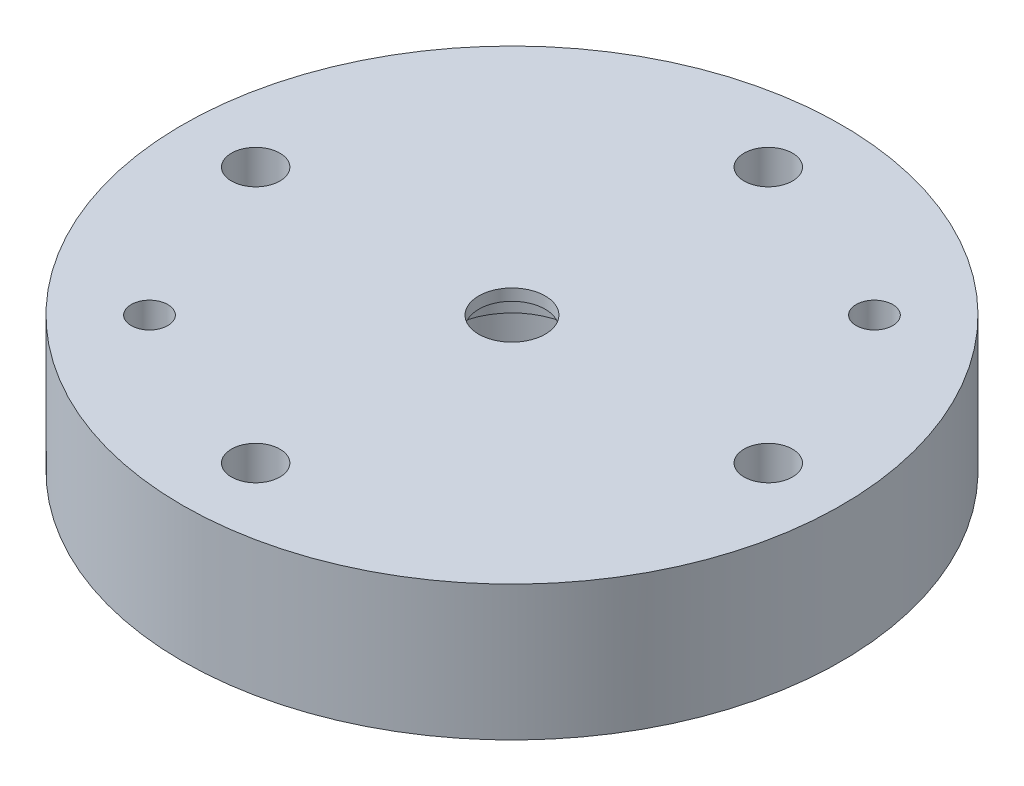
SolidWorks part; units mm, degrees
ref_plane "Front Plane" through (0, 0, 0) normal (0, 0, 1) x (1, 0, 0)
ref_plane "Top Plane" through (0, 0, 0) normal (0, 1, 0) x (1, 0, 0)
ref_plane "Right Plane" through (0, 0, 0) normal (1, 0, 0) x (0, 0, -1)
sketch "Sketch1" plane through (0, 0, 0) normal (0, 1, 0) x (1, 0, 0)
  circle A0 centre (0, 0) radius 57.15
  dimension "D1" = 114.3
extrude "seal seat hieght" add sketch "Sketch1" against normal blind 5.5372 contours A0
ref_plane "top end of seal" through (0, 0, 0) normal (0, 1, 0) x (1, 0, 0)
sketch "Sketch2" plane through (0, -5.5372, 0) normal (0, -1, 0) x (1, 0, 0)
  circle A1 centre (0, 0) radius 57.15
  circle A2 centre (0, 0) radius 57.15
  dimension "D1" = 0
extrude "seal diaphram hieght" add sketch "Sketch2" along normal blind 15.875
ref_plane "bottom end of seal" through (0, -21.4122, 0) normal (0, -1, 0) x (-1, 0, 0)
sketch "Sketch3" plane through (0, 0, 0) normal (0, 1, 0) x (1, 0, 0)
  circle A1 centre (0, 0) radius 57.15
  circle A2 centre (0, 0) radius 57.15
  dimension "D1" = 0
extrude "seal shoulder hieght" add sketch "Sketch3" along normal blind 2
sketch "Sketch4" plane through (0, -21.4122, 0) normal (0, -1, 0) x (1, 0, 0)
  circle A1 centre (0, 0) radius 57.15
  circle A2 centre (0, 0) radius 57.15
  dimension "D1" = 0
sketch "Sketch5" plane through (0, 0, 0) normal (0, 1, 0) x (1, 0, 0)
  circle A0 centre (0, 0) radius 11.1125
  dimension "D1" = 22.225
extrude "seal seat fit" cut sketch "Sketch5" against normal blind 5.5372
sketch "Sketch6" plane through (0, -21.4122, 0) normal (0, -1, 0) x (-1, 0, 0)
  circle A0 centre (0, 0) radius 12.7
  dimension "D1" = 25.4
sketch "Sketch7" plane through (0, 0, 0) normal (0, 1, 0) x (1, 0, 0)
  circle A0 centre (0, 0) radius 4.7625 construction
  circle A1 centre (0, 0) radius 5.7625
  dimension "D1" = 9.525
  dimension "D2" = 1
extrude "shaft clearance" cut sketch "Sketch7" along normal up to surface (2 mm away) up to face at (0, 2, 57.15)
sketch "bolt circle" plane through (0, 2, 0) normal (0, 1, 0) x (1, 0, 0)
  circle A0 centre (0, 0) radius 44.45 construction
  point P3 (-44.45, 0)
  point P4 (0, 44.45)
  point P5 (44.45, 0)
  point P6 (0, -44.45)
  dimension "D1" = 88.9
hole_wizard "M8 Clearance Hole1" positions "Sketch11" profile "Sketch12" hole size "M8" standard "ANSI Metric" end condition through all
sketch "Sketch11" plane through (0, 2, 0) normal (0, 1, 0) x (1, 0, 0)
  point P0 (-44.45, 0)
  point P3 (0, 44.45)
  point P6 (44.45, 0)
  point P9 (0, -44.45)
sketch "Sketch12" plane through (-44.45, 2, 0) normal (1, 0, 0) x (0, 0, 1)
  line L0 (0, 0) -> (0, 23.4122)
  line L1 (0, 23.4122) -> (4.2, 23.4122)
  line L2 (4.2, 23.4122) -> (4.2, 0)
  line L5 (4.2, 0) -> (0, 0)
  line L11 (0, -6.35) -> (0, 107.95) construction
  dimension "Thru Hole Dia." = 8.4
  dimension "Thru Hole Depth" = 23.4122
sketch "dowel hole positioning " plane through (0, 2, 0) normal (0, 1, 0) x (1, 0, 0)
  line L0 (0, 0) -> (53.8672, 0) construction
  line L1 (-31.4309, -31.4309) -> (31.4309, 31.4309) construction
  circle A0 centre (0, 0) radius 44.45 construction
  circle A1 centre (0, 0) radius 44.45 construction
  point P8 (0, 0)
  point P9 (31.4309, 31.4309)
  point P10 (-31.4309, -31.4309)
  dimension "D1" = 45
hole_wizard "1/4 (0.25) Press Dowel Hole1" positions "Sketch14" profile "Sketch15" hole size "1/4" standard "ANSI Inch" end condition through all
sketch "Sketch14" plane through (0, 2, 0) normal (0, 1, 0) x (1, 0, 0)
  point P0 (31.4309, 31.4309)
  point P3 (-31.4309, -31.4309)
sketch "Sketch15" plane through (31.4309, 2, -31.4309) normal (1, 0, 0) x (0, 0, 1)
  line L0 (0, 0) -> (0, 23.4122)
  line L1 (0, 23.4122) -> (3.175, 23.4122)
  line L2 (3.175, 23.4122) -> (3.175, 0)
  line L5 (3.175, 0) -> (0, 0)
  line L11 (0, -6.35) -> (0, 107.95) construction
  dimension "Thru Hole Dia." = 6.35
  dimension "Thru Hole Depth" = 23.4122
extrude "Cut-Extrude1" cut sketch "Sketch6" against normal up to surface (15.875 mm away) up to face at (0, -5.5372, 11.1125)
sketch "Sketch16" plane through (0, 2, 0) normal (0, 1, 0) x (1, 0, 0)
  line L1 (0, 0) -> (-140.97, 0)
  line L2 (0, 0) -> (0, 59.563)
  line L3 (0, 59.563) -> (-140.97, 59.563)
  line L5 (-140.97, 0) -> (-140.97, 59.563)
  dimension "D1" = 59.563
  dimension "D2" = 140.97
equation "\"seal seat height\"=5.5372"
equation "\"D1@seal seat hieght\" = \"seal seat height\""
equation "\"seal diaphram height\"=15.875"
equation "\"D1@seal diaphram hieght\" = \"seal diaphram height\""
equation "\"seal shoulder height\"=2"
equation "\"D1@seal shoulder hieght\" = \"seal shoulder height\""
equation "\"seal seat OD\"= .875in"
equation "\"D1@Sketch5\"=\"seal seat OD\""
equation "\"D1@seal seat fit\" = \"seal seat height\""
equation "\"seal diaphram clearance\"=25.4"
equation "\"D1@Sketch6\"=\"seal diaphram clearance\""
equation "\"seal ID\"=9.525"
equation "\"D1@Sketch7\"=\"seal ID\""
equation "\"bolt circle dia\"=88.9"
equation "\"D1@bolt circle\" = \"bolt circle dia\""
